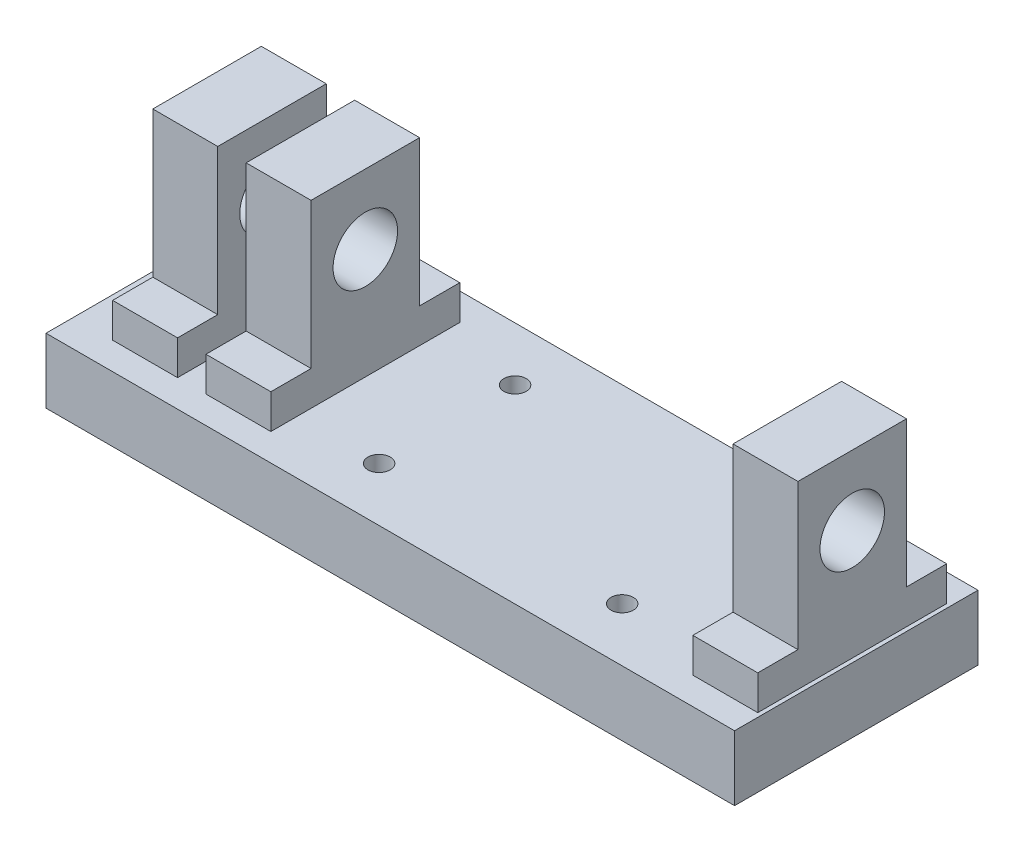
SolidWorks part; units mm, degrees
ref_plane "Front Plane" through (0, 0, 0) normal (0, 0, 1) x (1, 0, 0)
ref_plane "Top Plane" through (0, 0, 0) normal (0, 1, 0) x (1, 0, 0)
ref_plane "Right Plane" through (0, 0, 0) normal (1, 0, 0) x (0, 0, -1)
sketch "Sketch1" plane through (0, 0, 0) normal (0, 1, 0) x (1, 0, 0)
  line L0 (-18.75, -16.75) -> (46.65, -16.75) construction
  line L1 (-84.85, -30) -> (84.85, -30)
  line L2 (-84.85, -30) -> (-84.85, 30)
  line L3 (-84.85, 30) -> (84.85, 30)
  line L4 (84.85, -30) -> (84.85, 30)
  line L5 (-84.85, -30) -> (84.85, 30) construction
  line L6 (-84.85, 30) -> (84.85, -30) construction
  line L7 (-16, -16.75) -> (43.9, -16.75) construction
  line L8 (-16, -16.75) -> (-16, 16.75) construction
  line L9 (-16, 16.75) -> (43.9, 16.75) construction
  line L10 (43.9, -16.75) -> (43.9, 16.75) construction
  line L11 (43.9, 19.5) -> (43.9, -19.5) construction
  circle A0 centre (-16, -16.75) radius 2.75
  circle A1 centre (43.9, -16.75) radius 2.75
  circle A2 centre (43.9, 16.75) radius 2.75
  circle A3 centre (-16, 16.75) radius 2.75
  point P0 (0, 0)
  point P18 (43.9, 0)
  dimension "D2" = 5.5
  dimension "D1" = 60
  dimension "D3" = 65.4
  dimension "D4" = 39
  dimension "D5" = 38.2
  dimension "D6" = 66.1
extrude "Boss-Extrude1" add sketch "Sketch1" along normal blind 16
sketch "Sketch2" plane through (84.85, 0, 0) normal (1, 0, 0) x (0, 0, -1)
  line L0 (-30, 16) -> (30, 16) construction
  line L1 (-23.2808, 16) -> (23.2808, 16)
  line L2 (-23.2808, 16) -> (-23.2808, 24.5)
  line L3 (-23.2808, 24.5) -> (23.2808, 24.5)
  line L4 (23.2808, 16) -> (23.2808, 24.5)
  line L5 (0, 51.2) -> (0, 60.4) construction
  line L6 (-13.3741, 24.5) -> (13.3741, 24.5)
  line L7 (-13.3741, 24.5) -> (-13.3741, 60.4)
  line L8 (-13.3741, 60.4) -> (13.3741, 60.4)
  line L9 (13.3741, 24.5) -> (13.3741, 60.4)
  circle A0 centre (0, 43.25) radius 7.95
  point P11 (0, 60.4)
  point P12 (0, 24.5)
  point P13 (0, 16)
  point P18 (19.5, 16)
  point P19 (13.3741, 24.5)
  point P21 (19.5, 16)
  point P22 (23.2808, 16)
  line M13 (30, 16) -> (-30, 16)
  dimension "D4" = 15.9
  dimension "D1" = 44.4
  dimension "D2" = 8.5
  dimension "D3" = 9.2
extrude "Boss-Extrude2" add sketch "Sketch2" against normal blind 16 from offset 1 contours A0 L8 L7 L3 L9 | L4 L3 L2 M13 region at (84.85, 20.25, 0) region at (84.85, 42.45, 12.9264) offset against normal yes
pattern_linear "LPattern1" count 2 spacing 120 along (-1, 0, 0) of "Boss-Extrude2"
extrude "Boss-Extrude3" add sketch "Sketch2<3>" along normal blind 16 from offset 160 contours A0 L8 L7 L3 L9 | L4 L3 L2 M13 region at (84.85, 20.25, 0) region at (84.85, 42.45, 12.9264) offset against normal yes
sketch "Sketch2<3>" plane through (84.85, 0, 0) normal (1, 0, 0) x (0, 0, -1) same geometry as "Sketch2"
